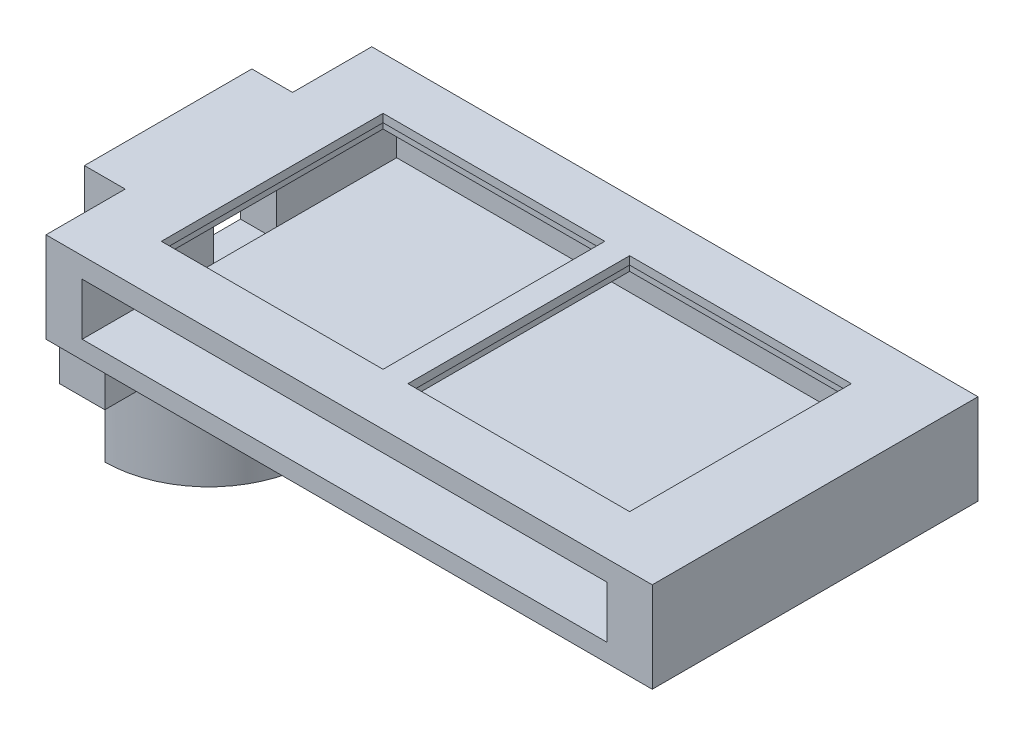
SolidWorks part; units mm, degrees
ref_plane "Front Plane" through (0, 0, 0) normal (0, 0, 1) x (1, 0, 0)
ref_plane "Top Plane" through (0, 0, 0) normal (0, 1, 0) x (1, 0, 0)
ref_plane "Right Plane" through (0, 0, 0) normal (1, 0, 0) x (0, 0, -1)
sketch "Sketch5" plane through (0, 0, 0) normal (0, 1, 0) x (1, 0, 0)
  line L0 (-124, 0) -> (-134, 0)
  line L1 (0, 0) -> (-1.9533, 0)
  line L2 (0, 0) -> (0, 72)
  line L3 (0, 72) -> (-134, 72)
  line L4 (-134, 0) -> (-134, 72)
  line L10 (-124, 0) -> (-1.9533, 0)
  dimension "D1" = 72
  dimension "D2" = 134
extrude "Main Body" add sketch "Sketch5" against normal blind 16 contours L1 L2 L3 L4 region at (-67, 0, -36)
sketch "Sketch8" plane through (0, 0, 0) normal (0, 0, 1) x (1, 0, 0)
  line L0 (-134, -16) -> (-134, 0) construction
  line L1 (0, -16) -> (-134, -16)
  line L2 (0, -16) -> (0, -20)
  line L3 (0, -20) -> (-134, -20)
  line L4 (-134, -16) -> (-134, -20)
  dimension "D1" = 4
extrude "Cover" add sketch "Sketch8" against normal up to surface (72 mm away) up to face at (-67, -8, -72)
sketch "Sketch20" plane through (0, 0, 0) normal (0, 0, 1) x (1, 0, 0)
  line L0 (-134, -20) -> (-134, 0) construction
  line L1 (-10, -4.5) -> (-126, -4.5)
  line L2 (-10, -4.5) -> (-10, -16)
  line L3 (-10, -16) -> (-126, -16)
  line L4 (-126, -4.5) -> (-126, -16)
  line L5 (0, -20) -> (0, 0) construction
  line L7 (-134, -20) -> (0, -20) construction
  dimension "D1" = 8
  dimension "D2" = 10
  dimension "D3" = 11.5
  dimension "D4" = 4
extrude "Crystal Slot" cut sketch "Sketch20" against normal offset from surface (69.5 mm away) 2.5 contours L2 L1 L4 L3 up to face at (-67, -10, -72)
sketch "Sketch9" plane through (-134, 0, 0) normal (-1, 0, 0) x (0, 0, 1)
  line L3 (-29, -4.5) -> (-43, -4.5)
  line L4 (-43, -18.5) -> (-43, -4.5)
  line L5 (-72, -20) -> (-72, 0) construction
  line L6 (-69.5, -4.5) -> (0, -4.5) construction
  line L7 (-29, -4.5) -> (-29, -18.5)
  line L8 (-29, -18.5) -> (-43, -18.5)
  dimension "D1" = 14
  dimension "D2" = 14
  dimension "D3" = 29
  dimension "D4" = 0
extrude "SiPM Window" cut sketch "Sketch9" against normal up to surface (8 mm away) up to face at (-126, -10.25, -34.75)
sketch "Sketch10" plane through (0, -20, 0) normal (0, -1, 0) x (1, 0, 0)
  line L0 (-134, -72) -> (-134, 0) construction
  line L4 (-134, -72) -> (-134, 0) construction
  line L5 (-134, -72) -> (0, -72) construction
  line L6 (-134, -16) -> (-134, -13)
  line L7 (-134, -56) -> (-134, -59)
  arc A0 (-134, -56) -> (-134, -16) centre (-134, -36) ccw
  arc A1 (-134, -59) -> (-134, -13) centre (-134, -36) ccw
  line M4 (-134, 0) -> (-134, -72)
  line M8 (-134, 0) -> (-134, -72)
  dimension "D2" = 20
  dimension "D1" = 36
  dimension "D3" = 3
  dimension "D4" = 3
extrude "Tube Adapter" add sketch "Sketch10" along normal blind 30 contours A1 A0 M4 M8 region at (-133.4857, -20, -14.5)
sketch "Sketch11" plane through (0, -20, 0) normal (0, -1, 0) x (1, 0, 0)
  line L0 (-134, -59) -> (-134, -69)
  line L5 (-134, -72) -> (-134, -59) construction
  line L6 (-134, -69) -> (-124, -69)
  line L7 (-124, -69) -> (-124, -56.7123)
  arc A0 (-134, -59) -> (-124, -56.7123) centre (-134, -36) ccw
  dimension "D1" = 10
  dimension "D2" = 10
extrude "Right Screw Terminal" add sketch "Sketch11" along normal blind 10
sketch "Sketch12" plane through (-134, 0, 0) normal (-1, 0, 0) x (0, 0, 1)
  line L2 (-69, -30) -> (-69, -20) construction
  line L3 (-59, -30) -> (-69, -30) construction
  circle A0 centre (-64, -25) radius 1.524
  dimension "D3" = 5
  dimension "D1" = 3.048
  dimension "D2" = 5
extrude "Right Screw Hole" cut sketch "Sketch12" against normal up to next
sketch "Sketch13" plane through (0, -20, 0) normal (0, -1, 0) x (-1, 0, 0)
  line L2 (134, 13) -> (134, 3)
  line L3 (134, 3) -> (124, 3)
  line L4 (124, 15.2877) -> (124, 3)
  arc A0 (134, 13) -> (124, 15.2877) centre (134, 36) cw
  dimension "D1" = 10
  dimension "D2" = 10
extrude "Left Screw Terminal" add sketch "Sketch13" along normal blind 10
sketch "Sketch14" plane through (-134, 0, 0) normal (-1, 0, 0) x (0, 0, 1)
  line L0 (-3, -30) -> (-3, -20) construction
  line L1 (-3, -30) -> (-13, -30) construction
  circle A0 centre (-8, -25) radius 1.524
  dimension "D3" = 3.048
  dimension "D1" = 5
  dimension "D2" = 5
extrude "Left Screw Hole" cut sketch "Sketch14" against normal up to next
sketch "Sketch15" plane through (-134, 0, 0) normal (-1, 0, 0) x (0, 0, 1)
  line L0 (-56, -20) -> (-16, -20) construction
  line L1 (-17.5, -20) -> (-54.5, -20)
  line L2 (-17.5, -20) -> (-17.5, 0)
  line L3 (-17.5, 0) -> (-54.5, 0)
  line L4 (-54.5, -20) -> (-54.5, 0)
  line L7 (0, 0) -> (-72, 0) construction
  line L8 (-43, -4.5) -> (-43, -18.5) construction
  dimension "D1" = 37
  dimension "D2" = 11.5
extrude "SiPM Mount" add sketch "Sketch15" along normal blind 9
sketch "Sketch17" plane through (0, -20, 0) normal (0, -1, 0) x (1, 0, 0)
  line L1 (-134, -18) -> (-142.8, -18)
  line L3 (-134, -54) -> (-142.8, -54)
  line L4 (-142.8, -18) -> (-142.8, -54)
  line L8 (-134, -18) -> (-134, -54)
  line L10 (-126, -29) -> (-134, -29) construction
  dimension "D1" = 36
  dimension "D2" = 11
  dimension "D3" = 8.8
extrude "SiPM Slot" cut sketch "Sketch17" against normal offset from surface (17.5 mm away) 2 up to face at (-99, -4.5, -35.375) offset beyond the face yes
ref_plane "Plane1" through (-144, 0, 0) normal (-1, 0, 0) x (0, 0, 1)
sketch "Sketch18" plane through (-144, 0, 0) normal (-1, 0, 0) x (0, 0, 1)
  line L0 (-56, -50) -> (-56, -20) construction
  line L5 (-56, -50) -> (-16, -50) construction
  circle A0 centre (-36, -42.5) radius 1.524
  dimension "D1" = 3.048
  dimension "D2" = 20
  dimension "D3" = 7.5
extrude "Adapter Hole" cut sketch "Sketch18" against normal up to surface (32.9495 mm away) up to face at (-124.4677, -32.5, -36)
sketch "Sketch21" plane through (0, -4.5, 0) normal (0, -1, 0) x (1, 0, 0)
  line L0 (-10, -69.5) -> (-10, 0) construction
  line L1 (-15, -10) -> (-67, -10)
  line L2 (-15, -10) -> (-15, -62)
  line L3 (-15, -62) -> (-67, -62)
  line L4 (-67, -10) -> (-67, -62)
  line L5 (-69.5, -10) -> (-121.5, -10)
  line L6 (-69.5, -10) -> (-69.5, -62)
  line L7 (-69.5, -62) -> (-121.5, -62)
  line L8 (-121.5, -10) -> (-121.5, -62)
  line L9 (-67, -36) -> (-15, -36) construction
  line L10 (0, -36) -> (-143, -36) construction
  line L11 (0, -72) -> (0, 0) construction
  line L12 (-143, -54.5) -> (-143, -17.5) construction
  line L13 (-121.5, -36) -> (-69.5, -36) construction
  dimension "D1" = 5
  dimension "D2" = 52
  dimension "D3" = 52
  dimension "D4" = 52
  dimension "D5" = 2.5
  dimension "D6" = 52
extrude "Filter Slot" cut sketch "Sketch21" against normal blind 2.7
sketch "Sketch24" plane through (0, -1.8, 0) normal (0, -1, 0) x (1, 0, 0)
  line L0 (-121.5, -10) -> (-121.5, -62) construction
  line L1 (-16.5, -11.5) -> (-65.5, -11.5)
  line L2 (-16.5, -11.5) -> (-16.5, -60.5)
  line L3 (-16.5, -60.5) -> (-65.5, -60.5)
  line L4 (-65.5, -11.5) -> (-65.5, -60.5)
  line L5 (-15, -10) -> (-67, -10) construction
  line L7 (-121.5, -62) -> (-69.5, -62) construction
  line L9 (-15, -62) -> (-15, -10) construction
  line L10 (-67, -62) -> (-15, -62) construction
  line L11 (-67, -10) -> (-67, -62) construction
  line L12 (-69.5, -10) -> (-121.5, -10) construction
  line L13 (-120, -11.5) -> (-71, -11.5)
  line L14 (-120, -11.5) -> (-120, -60.5)
  line L15 (-120, -60.5) -> (-71, -60.5)
  line L16 (-71, -11.5) -> (-71, -60.5)
  line L17 (-69.5, -62) -> (-69.5, -10) construction
  dimension "D1" = 1.5
  dimension "D2" = 1.5
  dimension "D3" = 1.5
  dimension "D4" = 1.5
  dimension "D5" = 1.5
  dimension "D6" = 1.5
  dimension "D7" = 1.5
  dimension "D8" = 1.5
extrude "Filter Window" cut sketch "Sketch24" against normal up to surface (1.8 mm away) up to face at (-102.75, 0, -36)
